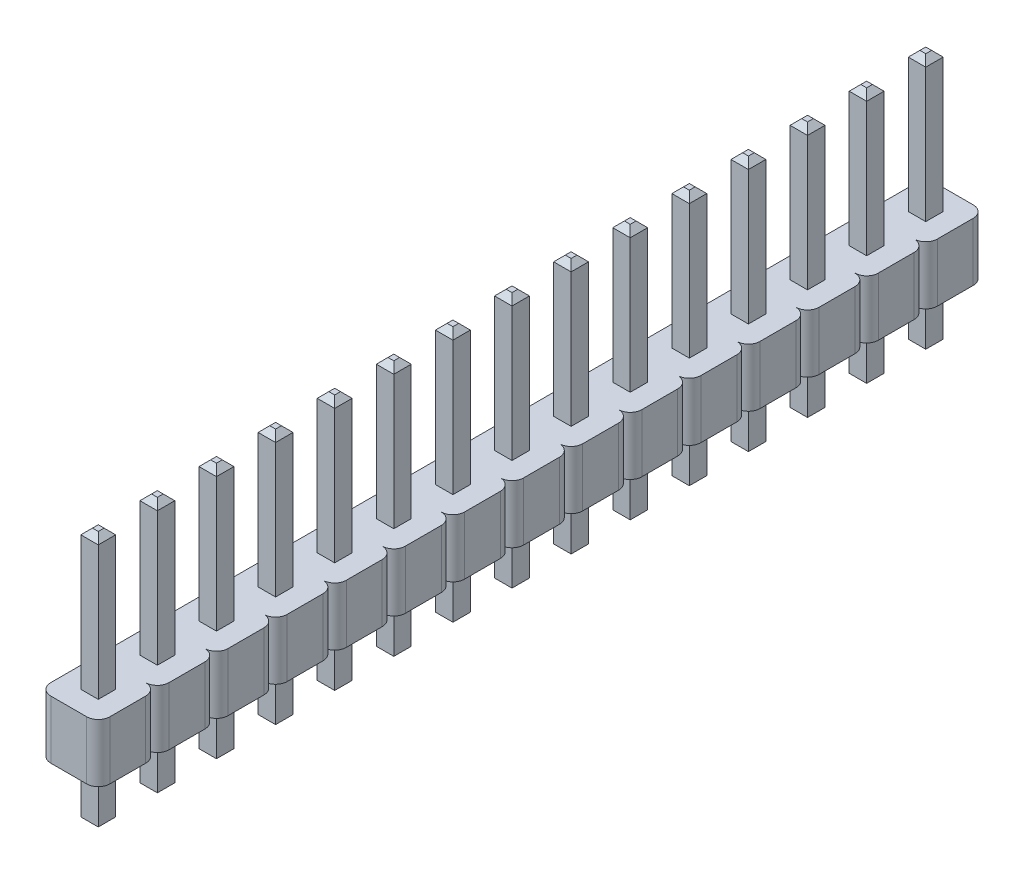
SolidWorks part; units mm, degrees
ref_plane "Front Plane" through (0, 0, 0) normal (0, 0, 1) x (1, 0, 0)
ref_plane "Top Plane" through (0, 0, 0) normal (0, 1, 0) x (1, 0, 0)
ref_plane "Right Plane" through (0, 0, 0) normal (1, 0, 0) x (0, 0, -1)
ref_plane "Plane1" through (0, 0, 0) normal (0, 1, 0) x (-1, 0, 0)
sketch "Sketch1" plane through (0, 0, 0) normal (0, 1, 0) x (-1, 0, 0)
  line L0 (-0.77, 1.27) -> (0.77, 1.27)
  line L1 (1.27, 0.77) -> (1.27, -0.77)
  line L2 (0.77, -1.27) -> (-0.77, -1.27)
  line L3 (-1.27, -0.77) -> (-1.27, 0.77)
  line L4 (-0.77, 0.77) -> (0.77, -0.77) construction
  arc A0 (1.27, 0.77) -> (0.77, 1.27) centre (0.77, 0.77) ccw
  arc A1 (0.77, -1.27) -> (1.27, -0.77) centre (0.77, -0.77) ccw
  arc A2 (-1.27, -0.77) -> (-0.77, -1.27) centre (-0.77, -0.77) ccw
  arc A3 (-0.77, 1.27) -> (-1.27, 0.77) centre (-0.77, 0.77) ccw
  dimension "D3" = 0.5
  dimension "D2" = 2.54
extrude "Boss-Extrude1" add sketch "Sketch1" along normal blind 2.5
ref_plane "Plane2" through (0.77, 0, 1.27) normal (-1, 0, 0) x (0, 0, 1)
ref_plane "Plane3" through (0.77, 0, 1.27) normal (0, -1, 0) x (0, 0, 1)
ref_axis "Axis1" through (0.77, 0, -79.63) along (0, 0, 1)
pattern_linear "LPattern1" count 15 spacing 2.54 along (0, 0, 1) of "Boss-Extrude1"
ref_plane "Plane4" through (0, 0, 0) normal (0, 1, 0) x (-1, 0, 0)
sketch "Sketch2" plane through (0, 0, 0) normal (0, 1, 0) x (-1, 0, 0)
  line L0 (-0.375, 0.375) -> (0.375, 0.375)
  line L1 (0.375, 0.375) -> (0.375, -0.375)
  line L2 (0.375, -0.375) -> (-0.375, -0.375)
  line L3 (-0.375, -0.375) -> (-0.375, 0.375)
  line L4 (-0.375, 0.375) -> (0.375, -0.375) construction
  dimension "D1" = 0.75
extrude "Boss-Extrude2" add sketch "Sketch2" along normal blind 8.5 and the other way blind 2.5
ref_plane "Plane5" through (0.3725, 0, 0.3725) normal (-1, 0, 0) x (0, 0, 1)
ref_plane "Plane6" through (0.3725, 0, 0.3725) normal (0, -1, 0) x (0, 0, 1)
ref_axis "Axis2" through (0.3725, 0, -80.5275) along (0, 0, 1)
chamfer "Chamfer1" distance 0.25 angle 45 8 edges at (0, -2.5, 0.375) (-0.375, -2.5, 0) (0.375, -2.5, 0) (0, -2.5, -0.375) (0, 8.5, 0.375) (-0.375, 8.5, 0) (0, 8.5, -0.375) (0.375, 8.5, 0)
pattern_linear "LPattern2" count 15 spacing 2.54 along (0, 0, 1) of "Boss-Extrude2", "Chamfer1"
ref_axis "Axis3" through (0, -3.575, 0) along (0, 1, 0)
